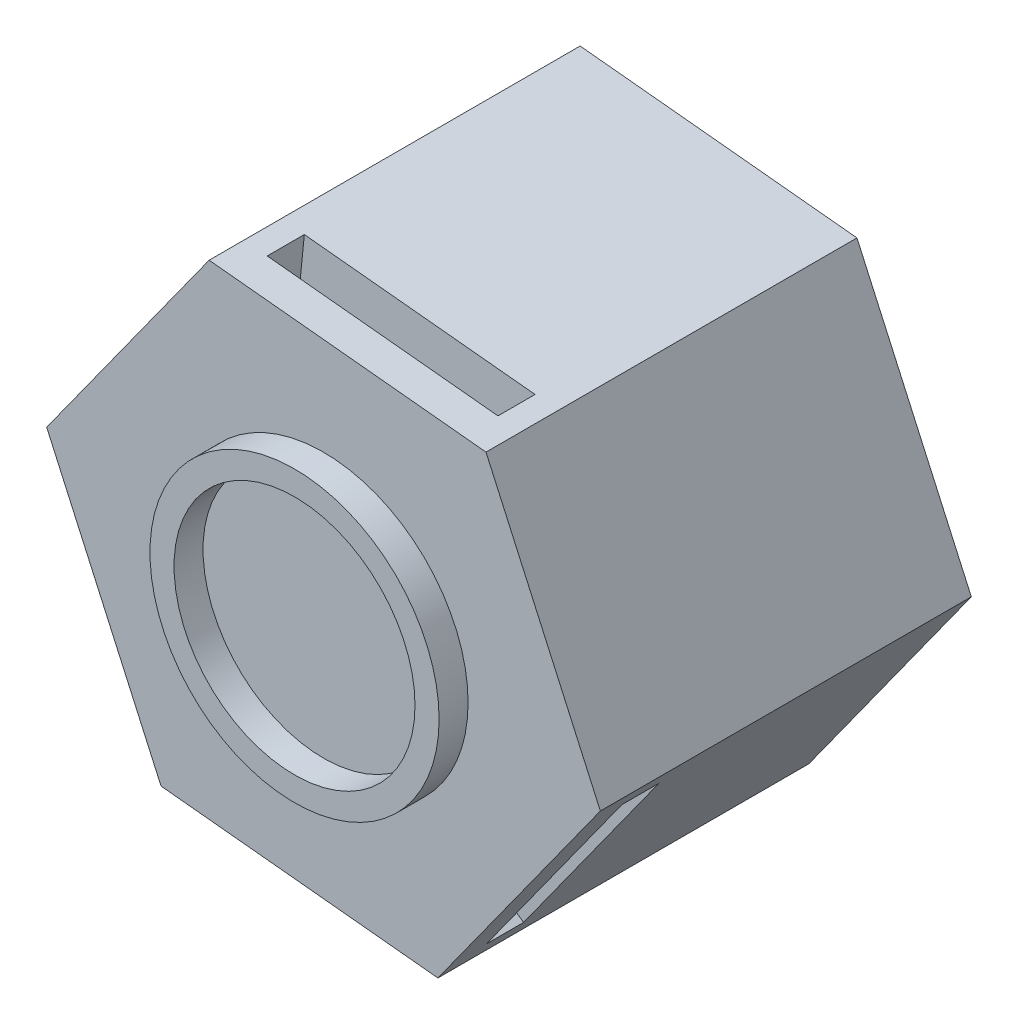
SolidWorks part; units mm, degrees
ref_plane "Ön Düzlem" through (0, 0, 0) normal (0, 0, 1) x (1, 0, 0)
ref_plane "Üst Düzlem" through (0, 0, 0) normal (0, 1, 0) x (1, 0, 0)
ref_plane "Sağ Düzlem" through (0, 0, 0) normal (1, 0, 0) x (0, 0, -1)
sketch "Çizim1" plane through (0, 0, 0) normal (0, 0, 1) x (1, 0, 0)
  line L1 (9.8651, -21.8788) -> (23.8801, -2.396)
  line L2 (23.8801, -2.396) -> (14.015, 19.4828)
  line L3 (14.015, 19.4828) -> (-9.8651, 21.8788)
  line L4 (-9.8651, 21.8788) -> (-23.8801, 2.396)
  line L5 (-23.8801, 2.396) -> (-14.015, -19.4828)
  line L6 (-14.015, -19.4828) -> (9.8651, -21.8788)
  circle A0 centre (0, 0) radius 20.7846 construction
  circle A1 centre (0, 0) radius 10.3923
  circle A2 centre (0, 0) radius 12.4708
  dimension "D1" = 24
extrude "Yükseklik-Ekstrüzyon1" add sketch "Çizim1" against normal blind 30 and the other way blind 2 contours L5 L6 L1 L2 L3 L4 A2 region at (-2.0103, -20.0363, 0)
extrude "Yükseklik-Ekstrüzyon2" add sketch "Çizim1<3>" against normal blind 30 and the other way blind 4.5 contours A2 A1 region at (-12.118, 0, 0)
sketch "Çizim1<3>" plane through (0, 0, 0) normal (0, 0, 1) x (1, 0, 0) same geometry as "Çizim1"
extrude "Yükseklik-Ekstrüzyon3" add sketch "Çizim1<4>" along normal blind 2 and the other way blind 30 contours A1 region at (0, 0, 0)
sketch "Çizim1<4>" plane through (0, 0, 0) normal (0, 0, 1) x (1, 0, 0) same geometry as "Çizim1"
sketch "Çizim4" plane through (16.8726, -12.1374, 0) normal (0.8118, -0.584, 0) x (0, 0, -1)
  line L1 (1.0221, 10) -> (4.2221, 10)
  line L2 (1.0221, 10) -> (1.0221, -10)
  line L3 (1.0221, -10) -> (4.2221, -10)
  line L4 (4.2221, 10) -> (4.2221, -10)
  line L5 (1.0221, 10) -> (4.2221, -10) construction
  line L6 (1.0221, -10) -> (4.2221, 10) construction
  point P0 (2.6221, 0)
extrude "Kes-Ekstrüzyon1" cut sketch "Çizim4" against normal blind 5
pattern_circular "Dairesel Kaplama1" count 3 over 360 about axis through (0, 0, 4.5) along (0, 0, -1) of "Kes-Ekstrüzyon1"
sketch "Çizim5" plane through (0, 0, -30) normal (0, 0, -1) x (-1, 0, 0)
  circle A0 centre (0, 0) radius 4
ref_plane "Düzlem1" through (0, 0, -41) normal (0, 0, -1) x (-1, 0, 0)
sketch "Çizim6" plane through (0, 0, -41) normal (0, 0, -1) x (-1, 0, 0)
  circle A0 centre (0, 0) radius 6
loft "Loft1" add profiles "Çizim6", "Çizim5" connector at (5.9988, 0.1206, -41) connector at (3.9999, 0.0327, -30)
